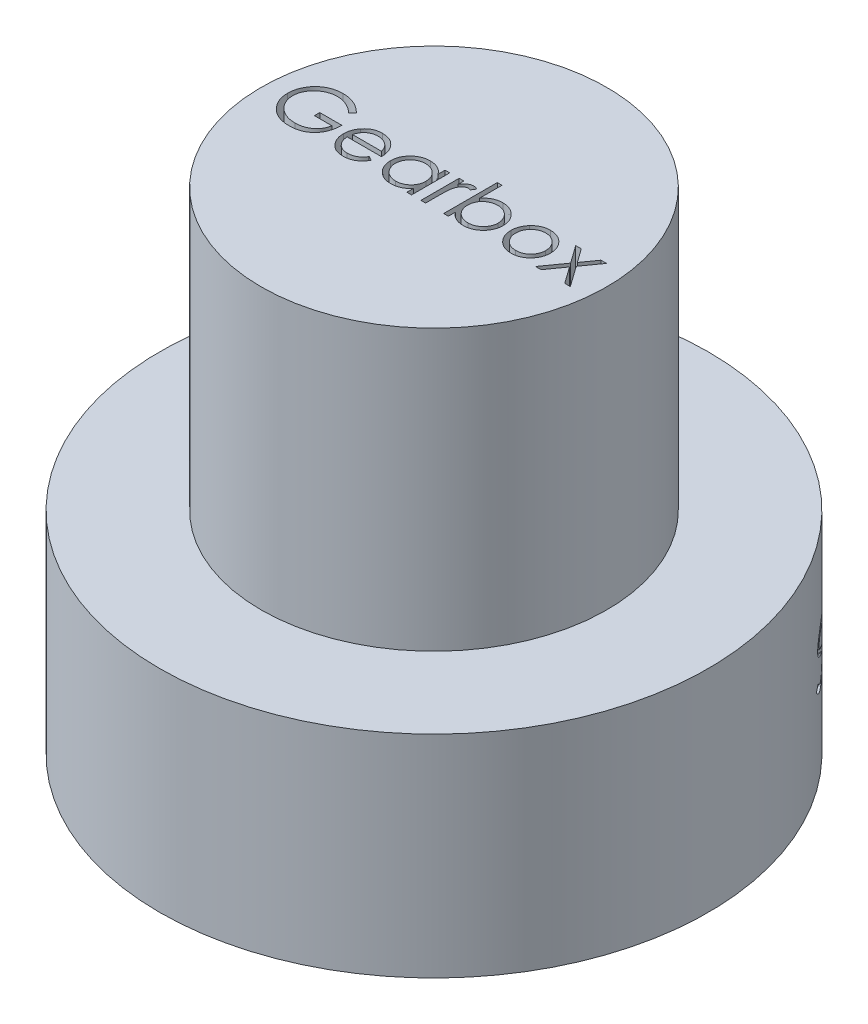
SolidWorks part; units mm, degrees
ref_plane "정면" through (0, 0, 0) normal (0, 0, 1) x (1, 0, 0)
ref_plane "윗면" through (0, 0, 0) normal (0, 1, 0) x (1, 0, 0)
ref_plane "우측면" through (0, 0, 0) normal (1, 0, 0) x (0, 0, -1)
sketch "Sketch1" plane through (0, 0, 0) normal (0, 1, 0) x (1, 0, 0)
  circle A0 centre (0, 0) radius 63
extrude "Boss-Extrude1" add sketch "Sketch1" along normal blind 102
sketch "Sketch2" plane through (0, 102, 0) normal (0, 1, 0) x (1, 0, 0)
  text T0 "Gearbox" font "Century Gothic" height in points 72
extrude "Cut-Extrude1" cut sketch "Sketch2" against normal blind 30
sketch "Sketch3" plane through (0, 0, 0) normal (0, -1, 0) x (1, 0, 0)
  circle A0 centre (0, 0) radius 100
extrude "Boss-Extrude2" add sketch "Sketch3" along normal blind 77
ref_plane "Plane1" through (0, 0, -100) normal (0, 0, 1) x (1, 0, 0)
sketch "Sketch4" plane through (0, 0, -100) normal (0, 0, 1) x (1, 0, 0)
  text T0 "Scatter Shield" font "Century Gothic" height in points 72
extrude "Cut-Extrude2" cut sketch "Sketch4" along normal blind 77
